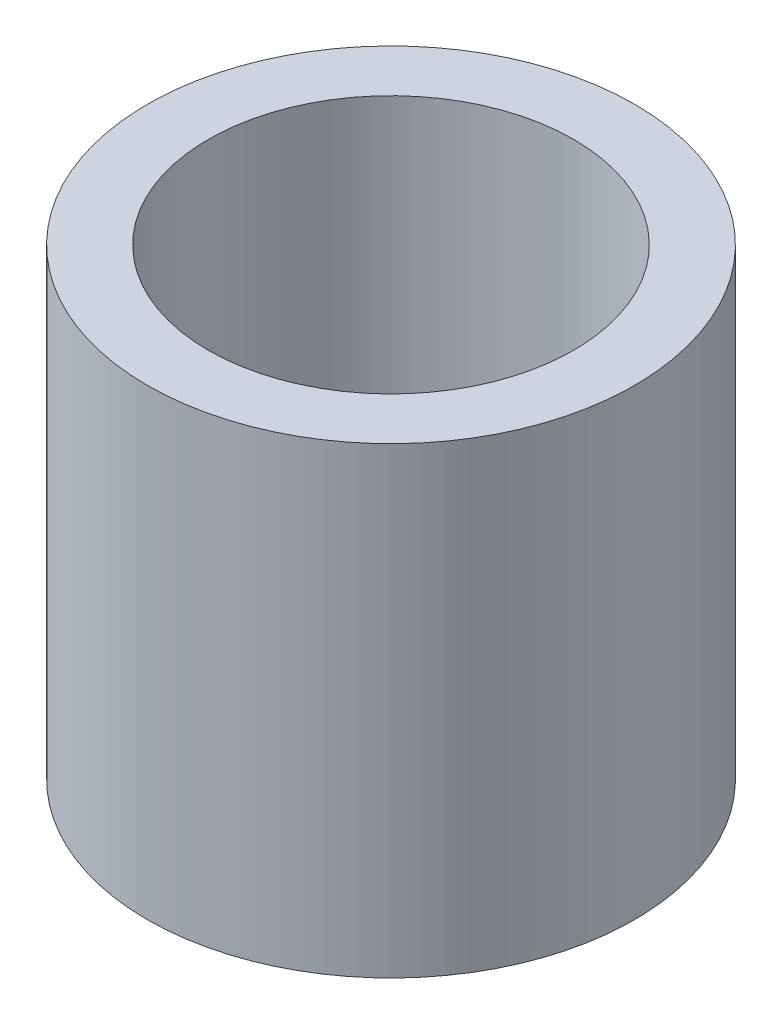
SolidWorks part; units mm, degrees
ref_plane "Front Plane" through (0, 0, 0) normal (0, 0, 1) x (1, 0, 0)
ref_plane "Top Plane" through (0, 0, 0) normal (0, 1, 0) x (1, 0, 0)
ref_plane "Right Plane" through (0, 0, 0) normal (1, 0, 0) x (0, 0, -1)
sketch "Sketch1" plane through (0, 0, 0) normal (0, 1, 0) x (1, 0, 0)
  circle A0 centre (0, 0) radius 6.35
  circle A1 centre (0, 0) radius 4.7625
  dimension "D1" = 12.7
  dimension "D2" = 9.525
extrude "Boss-Extrude1" add sketch "Sketch1" along normal blind 12.065
